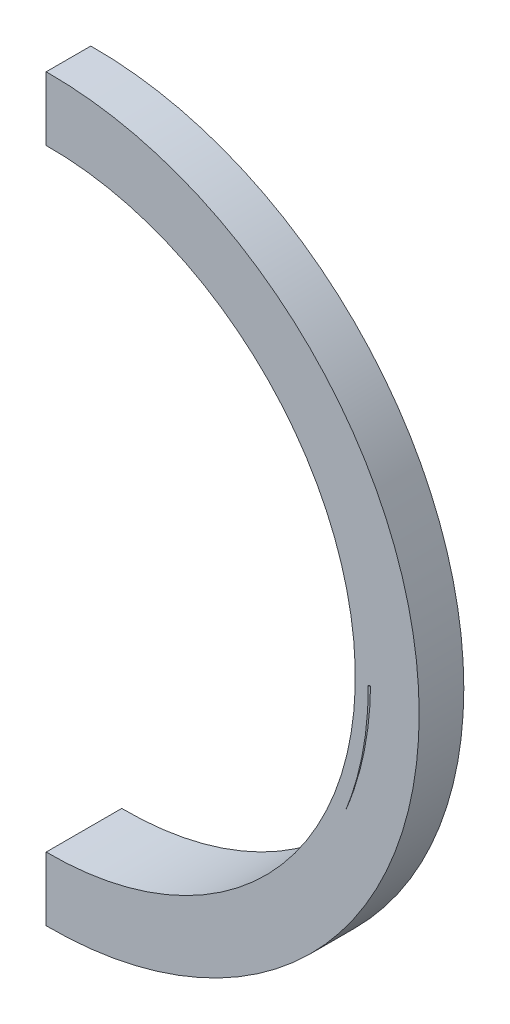
SolidWorks part; units mm, degrees
ref_plane "Front Plane" through (0, 0, 0) normal (0, 0, 1) x (1, 0, 0)
ref_plane "Top Plane" through (0, 0, 0) normal (0, 1, 0) x (1, 0, 0)
ref_plane "Right Plane" through (0, 0, 0) normal (1, 0, 0) x (0, 0, -1)
sketch "Sketch1" plane through (0, 0, 0) normal (0, 0, 1) x (1, 0, 0)
  circle A0 centre (0, 0) radius 53.85
  circle A1 centre (0, 0) radius 44.55
  dimension "D1" = 107.7
  dimension "D2" = 9.3
extrude "Boss-Extrude1" add sketch "Sketch1" along normal blind 6.5
sketch "Sketch2" plane through (0, 0, 0) normal (0, 0, -1) x (-1, 0, 0)
  circle A0 centre (0, 0) radius 44.55 construction
  circle A1 centre (0, 0) radius 44.55
  circle A2 centre (0, 0) radius 46.55
  dimension "D1" = 2
extrude "Boss-Extrude2" add sketch "Sketch2" along normal blind 4.5
thread "Thread1" pitch 1.5 method extrude profile "Thread Profile1" start angle 0, offset 0, length 10, pitch 2, diameter 93.1
ref_plane "Plane1" through (46.55, 0, -4.5) normal (0, -1, 0) x (1, 0, 0)
sketch "Thread Profile1" plane through (46.55, 0, -4.5) normal (0, -1, 0) x (1, 0, 0)
  line L0 (0, 0) -> (0, 1.5) construction
  line L1 (0, 0) -> (0.8119, 0.4687)
  line L2 (0.8119, 0.4687) -> (0.8119, 0.6562)
  line L3 (0.8119, 0.6562) -> (0, 1.125)
  line L4 (0.8119, 0.5625) -> (0, 0.5625) construction
  line L11 (0, 0) -> (0, 1.125)
  point P2 (0, 0)
  dimension "Pitch" = 1.5
  dimension "Profile_Angle" = 60
  dimension "Profile_Land" = 0.1875
  dimension "Profile_Height" = 0.8119
sketch "Sketch5" plane through (0, 0, 6.5) normal (0, 0, 1) x (1, 0, 0)
  line L0 (-0.4646, -116.7322) -> (-0.4646, 116.7322)
  line L1 (-87.9227, 116.7322) -> (86.9936, 116.7322)
  line L2 (-87.9227, 116.7322) -> (-87.9227, -116.7322)
  line L3 (-87.9227, -116.7322) -> (86.9936, -116.7322)
  line L4 (86.9936, 116.7322) -> (86.9936, -116.7322)
  line L5 (-87.9227, 116.7322) -> (86.9936, -116.7322) construction
  line L6 (-87.9227, -116.7322) -> (86.9936, 116.7322) construction
  point P0 (-0.7646, 0)
  point P10 (0, 0)
  circle M5 centre (0, 0) radius 53.85
  circle M6 centre (0, 0) radius 44.55
  dimension "D1" = 0.3
extrude "Cut-Extrude1" cut sketch "Sketch5" against normal through all contours L2 L3 L0 L1 M5 | L0 M6 | L0 M5 M6 region at (-44.1936, -114.2392, 6.5) region at (-52.648, 0, 6.5) region at (-19.1589, 0, 6.5)
